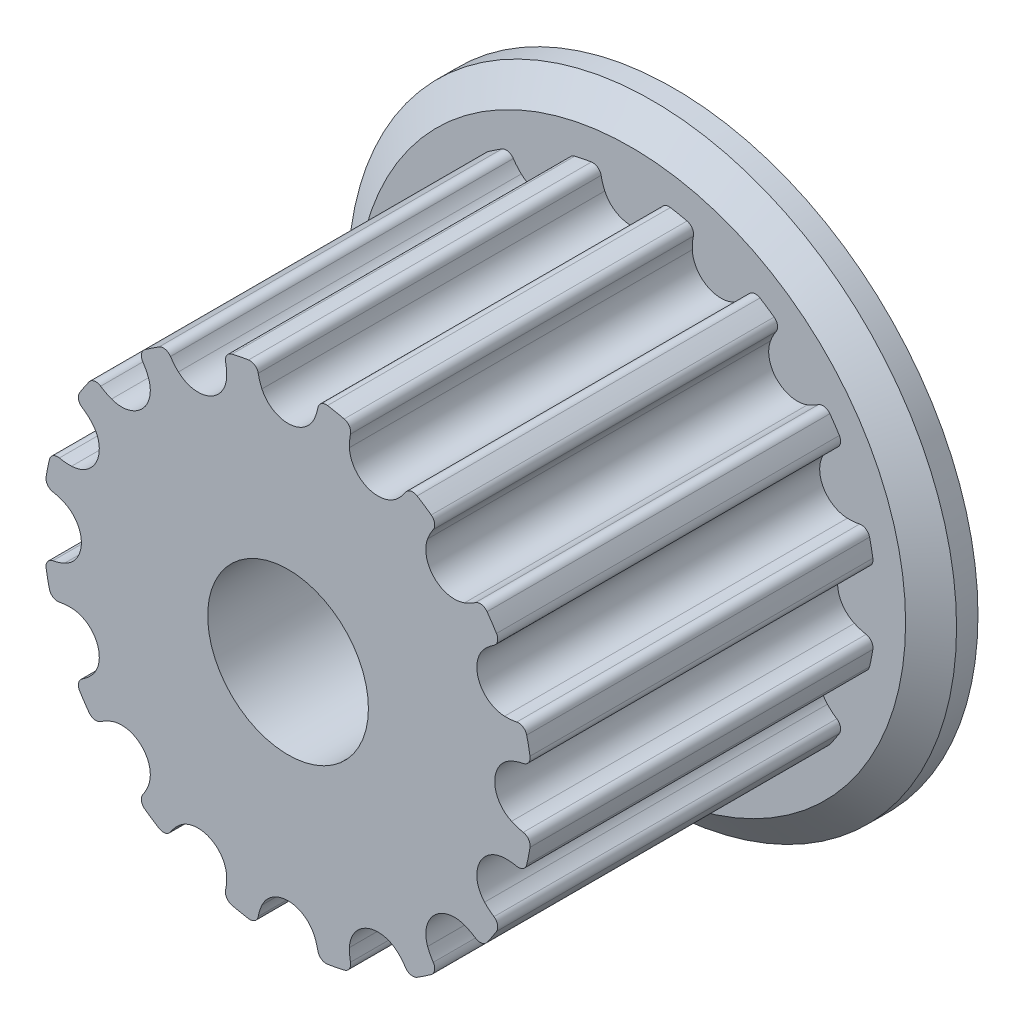
SolidWorks part; units mm, degrees
ref_plane "Front Plane" through (0, 0, 0) normal (0, 0, 1) x (1, 0, 0)
ref_plane "Top Plane" through (0, 0, 0) normal (0, 1, 0) x (1, 0, 0)
ref_plane "Right Plane" through (0, 0, 0) normal (1, 0, 0) x (0, 0, -1)
sketch "Sketch1" plane through (0, 0, 0) normal (0, 0, 1) x (1, 0, 0)
  line L1 (-2.553, 6.1245) -> (2.553, 6.1245) construction
  line L4 (0, 0) -> (0, 6.1245) construction
  line L5 (0, 6.1245) -> (0, 12.0565) construction
  line L6 (0, 7.6455) -> (2.9417, 7.0569) construction
  line L7 (2.9417, 7.0569) -> (3.8741, 6.6682) construction
  line L8 (2.9417, 7.0569) -> (2.553, 6.1245) construction
  line L9 (-2.9417, 7.0569) -> (-2.553, 6.1245) construction
  line L10 (-2.7951, 6.7052) -> (-3.7579, 9.015)
  line L11 (-3.7579, 9.015) -> (3.7579, 9.015)
  line L12 (3.7579, 9.015) -> (2.7951, 6.7052)
  circle A0 centre (0, 0) radius 7.6455 construction
  circle A1 centre (0, 0) radius 9.015 construction
  circle A2 centre (0, 0) radius 7.2645 construction
  arc A3 (-0.7739, 6.6229) -> (0.7739, 6.6229) centre (0, 6.9745) ccw
  arc A4 (-0.7739, 6.6229) -> (-0.8836, 6.9694) centre (0.61, 7.2516) cw
  arc A5 (-2.7951, 6.7052) -> (-1.1695, 7.1697) centre (0, 0) cw
  arc A6 (-0.8836, 6.9694) -> (-1.1695, 7.1697) centre (-1.1292, 6.923) ccw
  arc A7 (2.7951, 6.7052) -> (1.1695, 7.1697) centre (0, 0) ccw
  arc A8 (0.8836, 6.9694) -> (1.1695, 7.1697) centre (1.1292, 6.923) cw
  arc A9 (0.7739, 6.6229) -> (0.8836, 6.9694) centre (-0.61, 7.2516) ccw
  point P6 (0, 20.9083)
  point P11 (0, 7.6455)
  point P13 (0, 9.015)
  point P14 (0, 7.2645)
  dimension "D1" = 8.8518
  dimension "D2" = 4.411
sketch "Sketch2" plane through (0, 0, 0) normal (1, 0, 0) x (0, 0, -1)
  line L0 (-8.775, 2.3812) -> (8.775, 2.3812)
  line L1 (-8.775, 2.3812) -> (-8.775, 9.015)
  line L2 (-3.29, 9.015) -> (-8.775, 9.015)
  line L3 (-3.925, 2.3813) -> (-3.925, 9.015) construction
  line L4 (-3.925, 9.015) -> (-2.655, 9.015) construction
  line L5 (-2.655, 9.015) -> (-2.655, 7.2645) construction
  line L6 (-2.655, 7.2645) -> (7.505, 7.2645)
  line L7 (7.505, 7.2645) -> (7.505, 9.015) construction
  line L8 (7.505, 9.015) -> (8.775, 9.015) construction
  line L9 (8.775, 9.015) -> (8.775, 2.3812)
  line L10 (-8.775, 0) -> (8.775, 0) construction
  line L11 (8.14, 9.015) -> (7.505, 8.1398)
  line L12 (-2.655, 8.1398) -> (-3.29, 9.015)
  line L14 (-2.655, 8.1398) -> (-2.655, 7.2645)
  line L15 (7.505, 7.2645) -> (7.505, 8.1398)
  line L16 (8.14, 9.015) -> (8.775, 9.015)
  arc A0 (-2.655, 8.1398) -> (-3.29, 9.015) centre (-3.5757, 8.1398) ccw construction
  arc A1 (7.505, 8.1398) -> (8.14, 9.015) centre (8.4257, 8.1398) cw construction
  point P12 (-2.655, 8.1398)
  point P14 (-3.29, 9.015)
  point P20 (7.505, 8.1398)
  point P21 (8.14, 9.015)
  point P25 (7.505, 0)
  point P26 (-2.655, 0)
  dimension "OA" = 17.55
  dimension "Bore" = 4.7625
  dimension "Outside Width" = 11.43
  dimension "Inside Width" = 10.16
revolve "Revolve1" add sketch "Sketch2" angle 360 mid plane about L10
sketch "Sketch3" plane through (0, 0, 0) normal (0, 0, 1) x (1, 0, 0)
  line L6 (3.7579, 9.015) -> (-3.7579, 9.015)
  line L7 (2.7951, 6.7052) -> (3.7579, 9.015)
  line L8 (-3.7579, 9.015) -> (-2.7951, 6.7052)
  line L9 (3.7579, 9.015) -> (-3.7579, 9.015)
  line L10 (2.7951, 6.7052) -> (3.7579, 9.015)
  line L11 (-3.7579, 9.015) -> (-2.7951, 6.7052)
  arc A8 (2.7951, 6.7052) -> (1.1695, 7.1697) centre (0, 0) ccw
  arc A9 (1.1695, 7.1697) -> (0.8836, 6.9694) centre (1.1292, 6.923) ccw
  arc A10 (0.7739, 6.6229) -> (0.8836, 6.9694) centre (-0.61, 7.2516) ccw
  arc A11 (-0.7739, 6.6229) -> (0.7739, 6.6229) centre (0, 6.9745) ccw
  arc A12 (-0.8836, 6.9694) -> (-0.7739, 6.6229) centre (0.61, 7.2516) ccw
  arc A13 (-0.8836, 6.9694) -> (-1.1695, 7.1697) centre (-1.1292, 6.923) ccw
  arc A14 (-1.1695, 7.1697) -> (-2.7951, 6.7052) centre (0, 0) ccw
  arc A15 (2.7951, 6.7052) -> (1.1695, 7.1697) centre (0, 0) ccw
  arc A16 (1.1695, 7.1697) -> (0.8836, 6.9694) centre (1.1292, 6.923) ccw
  arc A17 (0.7739, 6.6229) -> (0.8836, 6.9694) centre (-0.61, 7.2516) ccw
  arc A18 (-0.7739, 6.6229) -> (0.7739, 6.6229) centre (0, 6.9745) ccw
  arc A19 (-0.8836, 6.9694) -> (-0.7739, 6.6229) centre (0.61, 7.2516) ccw
  arc A20 (-0.8836, 6.9694) -> (-1.1695, 7.1697) centre (-1.1292, 6.923) ccw
  arc A21 (-1.1695, 7.1697) -> (-2.7951, 6.7052) centre (0, 0) ccw
  dimension "D1" = 0
extrude "Cut-Extrude1" cut sketch "Sketch3" against normal up to vertex (7.505 mm away) from vertex up to point (0, 7.2645, -7.505) starting at point (0, 7.2645, 2.655)
pattern_circular "CirPattern1" count 16 over 360 about axis through (0, 0, 8.775) along (0, 0, 1) of "Cut-Extrude1"
sketch "Sketch4" plane through (0, 0, 0) normal (1, 0, 0) x (0, -1, 0)
  line L0 (0, -2.655) -> (0, -8.775) construction
  line L1 (-2.3812, -8.775) -> (2.3812, -8.775) construction
  line L2 (8.1398, -2.655) -> (-8.1398, -2.655) construction
  circle A0 centre (0, -5.715) radius 1.7526
extrude "Cut-Extrude2" cut sketch "Sketch4" along normal through all
ref_plane "Plane1" through (0, 0, 5.715) normal (0, 0, 1) x (1, 0, 0)
sketch "Sketch5" plane through (0, 0, 5.715) normal (0, 0, 1) x (1, 0, 0)
  line L0 (0, 0) -> (0, 9.015) construction
  line L1 (2.3812, -1.3716) -> (2.3812, 0)
  line L2 (2.7622, -1.7526) -> (8.462, -1.7526)
  line L3 (2.3812, 0) -> (9.015, 0) construction
  line L4 (2.3812, 0) -> (8.843, 0)
  line L5 (8.843, 0) -> (8.843, -1.3716)
  line L6 (2.7622, -1.7526) -> (2.3812, -1.3716)
  line L7 (8.843, -1.3716) -> (8.462, -1.7526)
  circle A0 centre (0, 0) radius 9.015 construction
  circle A1 centre (0, 0) radius 2.3812 construction
  point P2 (2.3812, -1.7526)
  point P11 (8.843, -1.7526)
revolve "Revolve2" add sketch "Sketch5" angle 360 mid plane about L4
sketch "Sketch6" plane through (8.843, 5.3841, 0) normal (-1, 0, 0) x (0, -1, 0)
  line L1 (5.3841, 6.7269) -> (4.5078, 6.2209)
  line L2 (4.5078, 6.2209) -> (4.5078, 5.2091)
  line L3 (4.5078, 5.2091) -> (5.3841, 4.7031)
  line L4 (5.3841, 4.7031) -> (6.2604, 5.2091)
  line L5 (6.2604, 5.2091) -> (6.2604, 6.2209)
  line L6 (6.2604, 6.2209) -> (5.3841, 6.7269)
  circle A0 centre (5.3841, 5.715) radius 0.8763 construction
  dimension "D1" = 1.7526
extrude "Cut-Extrude3" cut sketch "Sketch6" along normal blind 1.3144
pattern_circular "CirPattern3" count 2 over 90 about axis through (0, 0, 8.775) along (0, 0, 1) of "Cut-Extrude2", "Revolve2", "Cut-Extrude3"
chamfer "Chamfer1" distance 0.2807 angle 45 2 edges at (2.3812, 0, 8.775) (9.015, 0, 8.775)
ref_axis "Center Axis 1" through (0, 0, -8.775) along (0, 0, 1)
ref_plane "Contact Plane 1" through (0, 0, 8.775) normal (0, 0, 1) x (1, 0, 0)
ref_plane "Contact Plane 2" through (0, 0, -8.775) normal (0, 0, -1) x (-1, 0, 0)
sketch "Sketch7" plane through (0, 0, 8.775) normal (0, 0, 1) x (1, 0, 0)
  circle A0 centre (0, 0) radius 9.015 construction
  circle A1 centre (0, 0) radius 9.015
extrude "Cut-Extrude4" cut sketch "Sketch7" against normal up to surface (6.12 mm away) up to face at (0, 0, 2.655)
equation "\"D2@Sketch1\"= \"D1@Sketch1\" / 2"
equation "\"D1@Sketch6\" = \"Set Screw@Sketch4\" / 2"
equation "\"D1@Cut-Extrude3\" = \"D1@Sketch6\"*.75"
